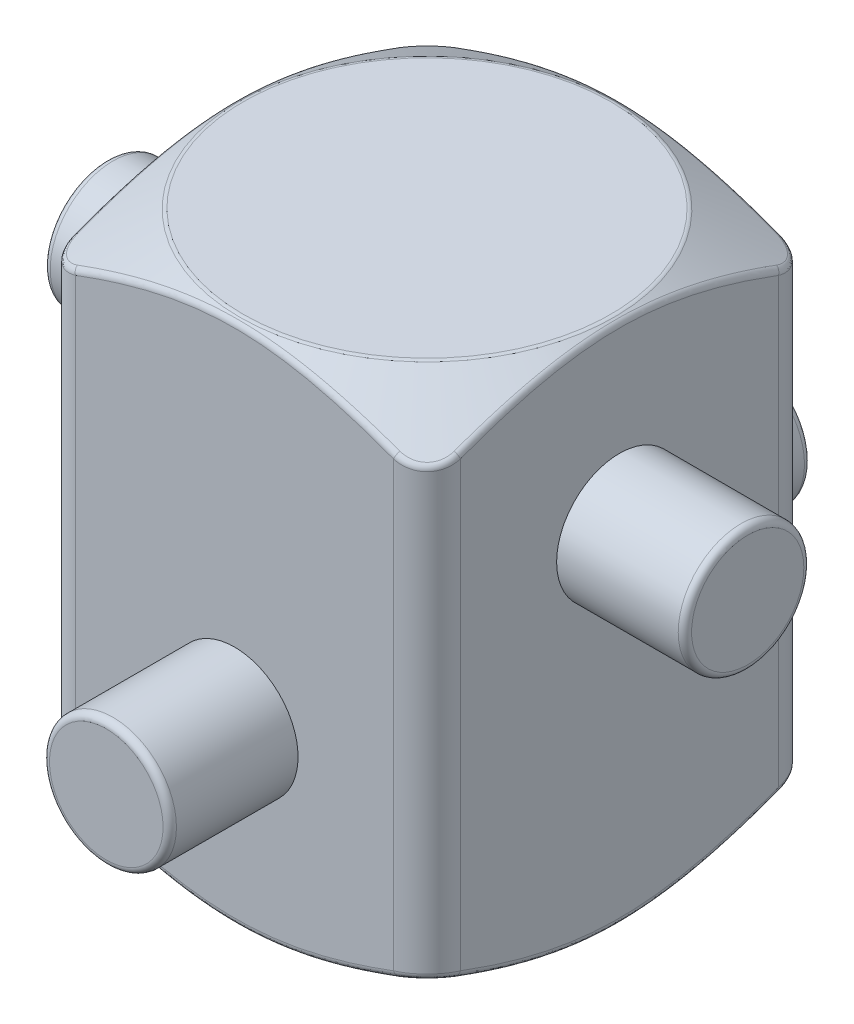
SolidWorks part; units mm, degrees
ref_plane "Front Plane" through (0, 0, 0) normal (0, 0, 1) x (1, 0, 0)
ref_plane "Top Plane" through (0, 0, 0) normal (0, 1, 0) x (1, 0, 0)
ref_plane "Right Plane" through (0, 0, 0) normal (1, 0, 0) x (0, 0, -1)
sketch "Sketch1" plane through (0, 0, 0) normal (0, 1, 0) x (1, 0, 0)
  line L1 (-7.2, -7.2) -> (7.2, -7.2)
  line L2 (-7.2, -7.2) -> (-7.2, 7.2)
  line L3 (-7.2, 7.2) -> (7.2, 7.2)
  line L4 (7.2, -7.2) -> (7.2, 7.2)
  line L5 (-7.2, -7.2) -> (7.2, 7.2) construction
  line L6 (-7.2, 7.2) -> (7.2, -7.2) construction
  point P0 (0, 0)
  dimension "D1" = 14.4
extrude "Boss-Extrude1" add sketch "Sketch1" along normal blind 19.7
ref_axis "Axis1" through (0, 33.0449, 0) along (0, -1, 0)
sketch "Sketch2" plane through (0, 0, 0) normal (0, 0, 1) x (1, 0, 0)
  line L0 (-7.2, 19.7) -> (-6.95, 19.7)
  line L1 (7.2, 19.7) -> (-7.2, 19.7) construction
  line L2 (-7.2, 19.7) -> (-15.84, 19.7)
  line L3 (-15.84, 19.7) -> (-15.84, 0)
  line L4 (-15.84, 0) -> (-6.95, 0)
  line L5 (7.2, 0) -> (-7.2, 0) construction
  line L6 (-6.95, 0) -> (-13.3, 3.6662)
  line L7 (-13.3, 3.6662) -> (-13.3, 16.0338)
  line L8 (-13.3, 16.0338) -> (-6.95, 19.7)
  dimension "D1" = 0.25
  dimension "D2" = 6.35
  dimension "D3" = 8.89
  dimension "D4" = 30
  dimension "D5" = 30
revolve "Cut-Revolve1" cut sketch "Sketch2" angle 360 about axis through (0, 33.0449, 0) along (0, -1, 0)
sketch "Sketch4" plane through (0, 0, 0) normal (0, 0, 1) x (1, 0, 0)
  line L0 (0, 33.0449) -> (0, -25.6198) construction
  circle A0 centre (0, 6.7) radius 2.375
  dimension "D1" = 4.75
  dimension "D2" = 6.7
extrude "Boss-Extrude3" add sketch "Sketch4" along normal mid plane 24
sketch "Sketch5" plane through (0, 0, 0) normal (1, 0, 0) x (0, 0, -1)
  line L0 (0, 33.0449) -> (0, -25.6198) construction
  line L1 (6.95, 19.7) -> (-6.95, 19.7) construction
  circle A0 centre (0, 13) radius 2.35
  dimension "D1" = 4.7
  dimension "D2" = 6.7
extrude "Boss-Extrude4" add sketch "Sketch5" along normal mid plane 24
fillet "Fillet1" radius 1.25 4 edges at (7.2, 9.85, -7.2) (-7.2, 9.85, -7.2) (-7.2, 9.85, 7.2) (7.2, 9.85, 7.2)
fillet "Fillet2" radius 0.25 22 edges at (6.9494, 1.561, 6.7009) (-0.7985, 0.1698, 7.2) (-6.7009, 1.561, 6.9494) (-7.2, 0.1698, -0.7985) (-6.9494, 1.561, -6.7009) (-0.7985, 0.1698, -7.2) (6.7009, 1.561, -6.9494) (-0.7985, 19.5302, -7.2) (6.9494, 18.139, -6.7009) (7.2, 19.5302, -0.7985) (6.7009, 18.139, 6.9494) (-0.7985, 19.5302, 7.2) (-6.9494, 18.139, 6.7009) (-7.2, 19.5302, -0.7985) (0, 19.7, 6.95) (7.2, 0.1698, -0.7985) (0, 0, 6.95) (-6.7009, 18.139, -6.9494) (12, 13, -2.35) (2.375, 6.7, 12) (2.375, 6.7, -12) (-12, 13, -2.35)
